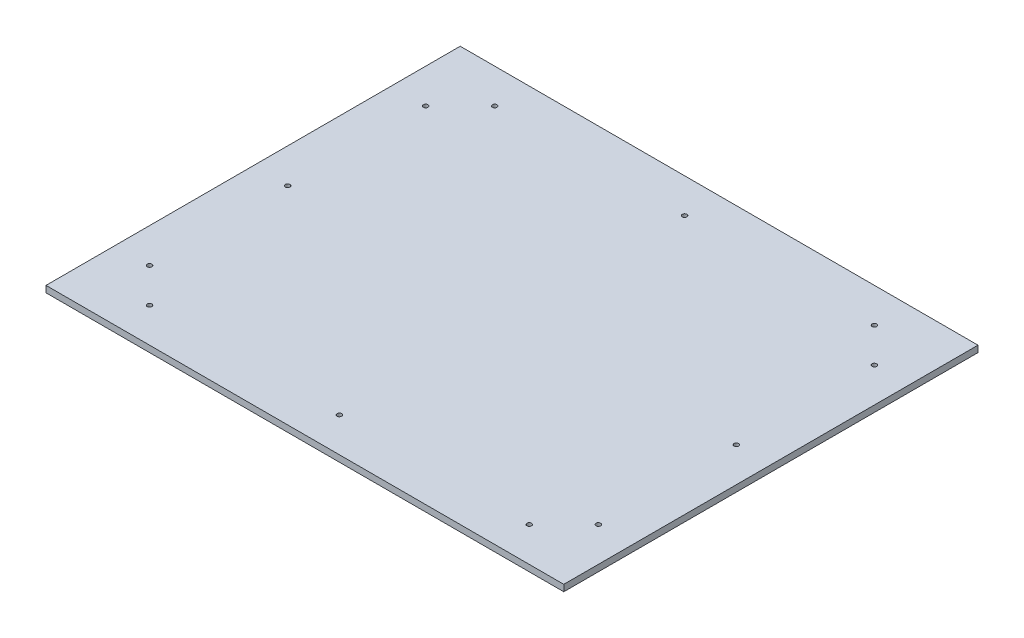
SolidWorks part; units mm, degrees
material "6061 Alloy"
ref_plane "Front Plane" through (0, 0, 0) normal (0, 0, 1) x (1, 0, 0)
ref_plane "Top Plane" through (0, 0, 0) normal (0, 1, 0) x (1, 0, 0)
ref_plane "Right Plane" through (0, 0, 0) normal (1, 0, 0) x (0, 0, -1)
sketch "Sketch1" plane through (0, 0, 0) normal (0, 1, 0) x (1, 0, 0)
  line L1 (-190.5, -152.4) -> (190.5, -152.4)
  line L2 (-190.5, -152.4) -> (-190.5, 152.4)
  line L3 (-190.5, 152.4) -> (190.5, 152.4)
  line L4 (190.5, -152.4) -> (190.5, 152.4)
  line L5 (-190.5, -152.4) -> (190.5, 152.4) construction
  line L6 (-190.5, 152.4) -> (190.5, -152.4) construction
  point P0 (0, 0)
  dimension "D1" = 304.8
  dimension "D2" = 381
extrude "Boss-Extrude1" add sketch "Sketch1" along normal blind 4.7625
sketch "Sketch2" plane through (0, 4.7625, 0) normal (0, 1, 0) x (1, 0, 0)
  line L0 (-165.1, 152.4) -> (-165.1, -152.4) construction
  line L1 (190.5, 152.4) -> (-190.5, 152.4) construction
  line L2 (-190.5, -152.4) -> (190.5, -152.4) construction
  line L3 (-190.5, -127) -> (190.5, -127) construction
  line L4 (-190.5, 152.4) -> (-190.5, -152.4) construction
  line L5 (190.5, -152.4) -> (190.5, 152.4) construction
  line L6 (-190.5, 127) -> (190.5, 127) construction
  line L7 (165.1, 152.4) -> (165.1, -152.4) construction
  point P16 (-165.1, 0)
  point P17 (0, -127)
  point P18 (165.1, 0)
  point P19 (0, 127)
  point P20 (-165.1, 101.6)
  point P21 (-165.1, -101.6)
  point P22 (-139.7, 127)
  point P23 (-139.7, -127)
  point P24 (139.7, 127)
  point P25 (139.7, -127)
  point P26 (165.1, 101.6)
  point P27 (165.1, -101.6)
  dimension "D1" = 25.4
  dimension "D2" = 25.4
  dimension "D3" = 25.4
  dimension "D4" = 25.4
  dimension "D5" = 50.8
  dimension "D6" = 50.8
  dimension "D7" = 50.8
  dimension "D8" = 50.8
hole_wizard "M3 Clearance Hole1" positions "3DSketch1" profile "Sketch3" hole size "M3" standard "ANSI Metric" end condition through all
sketch3d "3DSketch1"
  point P0 (-165.1, 4.7625, 101.6)
  point P3 (-165.1, 4.7625, 0)
  point P10 (-165.1, 4.7625, -101.6)
  point P13 (-139.7, 4.7625, -127)
  point P16 (0, 4.7625, -127)
  point P19 (139.7, 4.7625, -127)
  point P22 (165.1, 4.7625, -101.6)
  point P25 (165.1, 4.7625, 0)
  point P28 (165.1, 4.7625, 101.6)
  point P31 (139.7, 4.7625, 127)
  point P34 (0, 4.7625, 127)
  point P37 (-139.7, 4.7625, 127)
sketch "Sketch3" plane through (-165.1, 4.7625, 101.6) normal (1, 0, 0) x (0, 0, 1)
  line L0 (0, 0) -> (0, 4.7625)
  line L1 (0, 4.7625) -> (1.7, 4.7625)
  line L2 (1.7, 4.7625) -> (1.7, 0)
  line L5 (1.7, 0) -> (0, 0)
  line L11 (0, -6.35) -> (0, 107.95) construction
  dimension "Thru Hole Dia." = 3.4
  dimension "Thru Hole Depth" = 4.7625
equation "\"D3@Sketch2\"=\"D1@Sketch2\""
equation "\"D4@Sketch2\"=\"D2@Sketch2\""
equation "\"D6@Sketch2\"=\"D5@Sketch2\""
equation "\"D7@Sketch2\"=\"D5@Sketch2\""
equation "\"D8@Sketch2\"=\"D5@Sketch2\""
